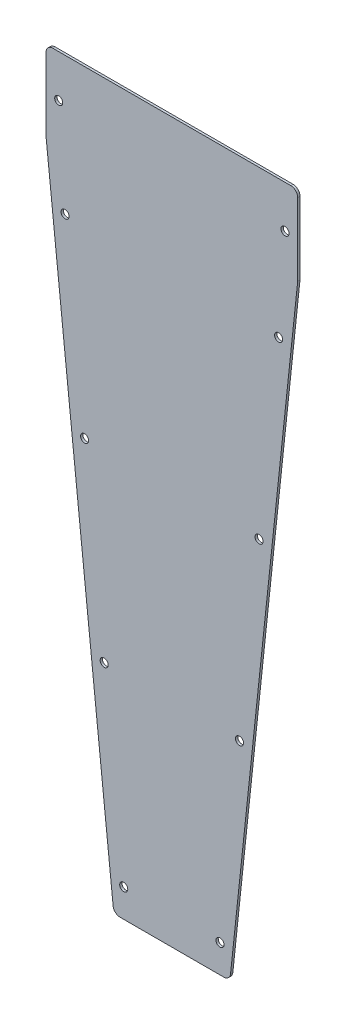
SolidWorks part; units mm, degrees
material "AISI 1020"
ref_plane "Plano frontal" through (0, 0, 0) normal (0, 0, 1) x (1, 0, 0)
ref_plane "Plano superior" through (0, 0, 0) normal (0, 1, 0) x (1, 0, 0)
ref_plane "Plano direito" through (0, 0, 0) normal (1, 0, 0) x (0, 0, -1)
sketch "Esboço1" plane through (0, 0, 0) normal (0, 0, 1) x (1, 0, 0)
  line L0 (-44.875, 0) -> (44.875, 0)
  line L1 (50.8416, 5.3674) -> (109, 553.95)
  line L2 (109, 553.95) -> (109, 616.76)
  line L3 (103, 622.76) -> (-103, 622.76)
  line L4 (-109, 616.76) -> (-109, 553.95)
  line L5 (-109, 553.95) -> (-50.8416, 5.3674)
  line L6 (0, 0) -> (0, 622.76) construction
  line L7 (-98, 586.08) -> (98, 586.08) construction
  line L8 (-92.5, 503.64) -> (92.5, 503.64) construction
  line L9 (-92.5, 503.64) -> (-75.5619, 343.87) construction
  line L10 (-75.5619, 343.87) -> (-58.6237, 184.1) construction
  line L11 (-58.6237, 184.1) -> (-41.6856, 24.33) construction
  arc A0 (-103, 622.76) -> (-109, 616.76) centre (-103, 616.76) ccw
  arc A1 (109, 616.76) -> (103, 622.76) centre (103, 616.76) ccw
  arc A2 (44.875, 0) -> (50.8416, 5.3674) centre (44.875, 6) ccw
  arc A3 (-44.875, 0) -> (-50.8416, 5.3674) centre (-44.875, 6) cw
  circle A4 centre (-98, 586.08) radius 3.5
  circle A5 centre (98, 586.08) radius 3.5
  circle A6 centre (-92.5, 503.64) radius 3.5
  circle A7 centre (92.5, 503.64) radius 3.5
  circle A8 centre (-75.5619, 343.87) radius 3.5
  circle A9 centre (-58.6237, 184.1) radius 3.5
  circle A10 centre (-41.6856, 24.33) radius 3.5
  circle A11 centre (41.6856, 24.33) radius 3.5
  circle A12 centre (58.6237, 184.1) radius 3.5
  circle A13 centre (75.5619, 343.87) radius 3.5
  point P9 (0, 622.76)
  point P15 (109, 622.76)
  point P33 (41.6856, 24.33)
  point P34 (58.6237, 184.1)
  point P35 (75.5619, 343.87)
  dimension "D3" = 6
  dimension "D4" = 6
  dimension "D7" = 7
  dimension "D12" = 7
  dimension "D1" = 622.76
  dimension "D2" = 68.81
  dimension "D5" = 218
  dimension "D6" = 89.75
  dimension "D8" = 196
  dimension "D9" = 36.68
  dimension "D10" = 119.12
  dimension "D11" = 185
  dimension "D13" = 159.77
base flange "Flange-base1" sketch "Esboço1" thickness 2 reverse thickness direction no parameters "D1"=0.7366
sketch "Curva-Linhas1" [suppressed] plane through (0, 0, 0) normal (0, 1, 0) x (1, 0, 0)
sketch "Caixa delimitadora1" [suppressed] plane through (0, 0, 0) normal (0, 1, 0) x (1, 0, 0)
sheet metal parameters "Chapa metálica1" thickness 2 parameters "D1"=0.7366
flat pattern "Padrão-Plano1" [suppressed]
sketch "Curva-Linhas2" plane through (0, 0, 0) normal (0, 1, 0) x (1, 0, 0)
sketch3d "Caixa delimitadora2" [suppressed]
  line L0 (-6, -616.76, 0) -> (-6, 6, 0) construction
  line L1 (212, -616.76, 0) -> (212, 6, 0) construction
  line L2 (-6, -616.76, 0) -> (212, -616.76, 0) construction
  line L3 (-6, 6, 0) -> (212, 6, 0) construction
